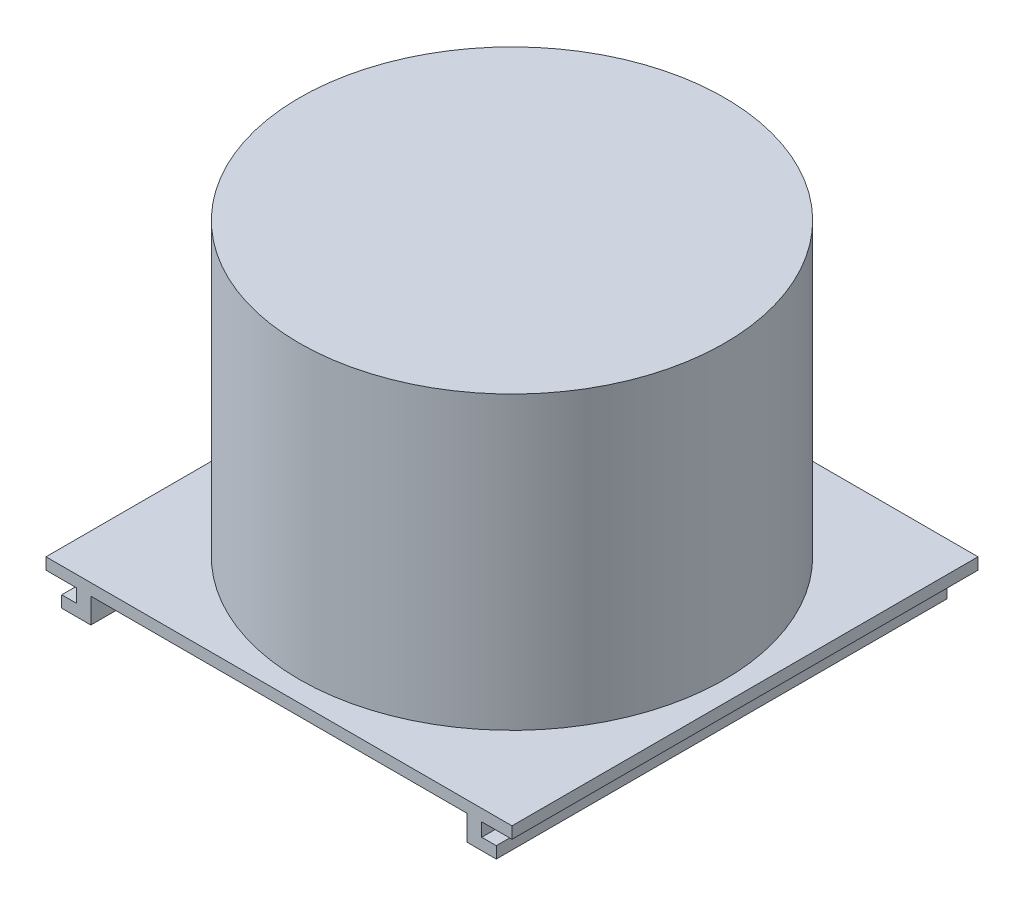
SolidWorks part; units mm, degrees
ref_plane "Front Plane" through (0, 0, 0) normal (0, 0, 1) x (1, 0, 0)
ref_plane "Top Plane" through (0, 0, 0) normal (0, 1, 0) x (1, 0, 0)
ref_plane "Right Plane" through (0, 0, 0) normal (1, 0, 0) x (0, 0, -1)
sketch "Sketch1" plane through (0, 0, 0) normal (0, 1, 0) x (1, 0, 0)
  line L1 (-40, -40) -> (40, -40)
  line L2 (-40, -40) -> (-40, 40)
  line L3 (-40, 40) -> (40, 40)
  line L4 (40, -40) -> (40, 40)
  line L5 (-40, -40) -> (40, 40) construction
  line L6 (-40, 40) -> (40, -40) construction
  circle A0 centre (0, 0) radius 35
  circle A1 centre (0, 0) radius 36.5
  point P0 (0, 0)
  dimension "D2" = 70
  dimension "D3" = 1.5
  dimension "D1" = 80
extrude "Boss-Extrude3" add sketch "Sketch1" against normal blind 2 contours L1 L4 L3 L2 A1 | A1 A0 region at (-38.8686, 0, 0) region at (-35.4676, 0, 0)
extrude "Boss-Extrude4" add sketch "Sketch1<7>" along normal blind 50 contours A1 A0 region at (-35.4676, 0, 0)
sketch "Sketch1<7>" plane through (0, 0, 0) normal (0, 1, 0) x (1, 0, 0) same geometry as "Sketch1"
sketch "Sketch3" plane through (0, 0, 40) normal (0, 0, 1) x (1, 0, 0)
  line L0 (-34.8, -2) -> (-32.3, -2)
  line L1 (-40, -2) -> (40, -2) construction
  line L2 (-32.3, -2) -> (-32.3, -6.3)
  line L3 (-32.3, -6.3) -> (-37.3, -6.3)
  line L4 (-37.3, -6.3) -> (-37.3, -4.3)
  line L5 (-37.3, -4.3) -> (-34.8, -4.3)
  line L6 (-34.8, -4.3) -> (-34.8, -2)
  line L8 (-40, -2) -> (-40, 0) construction
  line L9 (0, 0) -> (0, -6.3)
  line L10 (-40, 0) -> (40, 0) construction
  line L11 (37.3, -4.3) -> (34.8, -4.3)
  line L12 (37.3, -6.3) -> (37.3, -4.3)
  line L13 (32.3, -6.3) -> (37.3, -6.3)
  line L14 (32.3, -2) -> (32.3, -6.3)
  line L15 (34.8, -2) -> (32.3, -2)
  line L16 (34.8, -4.3) -> (34.8, -2)
  point P4 (-37.3, -5.3)
  line M10 (-40, -2) -> (40, -2)
  dimension "D1" = 2.5
  dimension "D2" = 2.7
  dimension "D3" = 2.3
  dimension "D4" = 2
  dimension "D5" = 2.5
extrude "Boss-Extrude5" add sketch "Sketch3" against normal offset from surface (77.35 mm away) 2.65 contours L6 L5 L4 L3 L2 M10 | L13 L12 L11 L16 L15 L14 region at (-34.3437, -4.5151, 40) up to face at (0, -1, -40)
sketch "Sketch4" plane through (0, 50, 0) normal (0, 1, 0) x (1, 0, 0)
  circle A0 centre (0, 0) radius 36
extrude "Boss-Extrude6" add sketch "Sketch4" against normal blind 1.5
